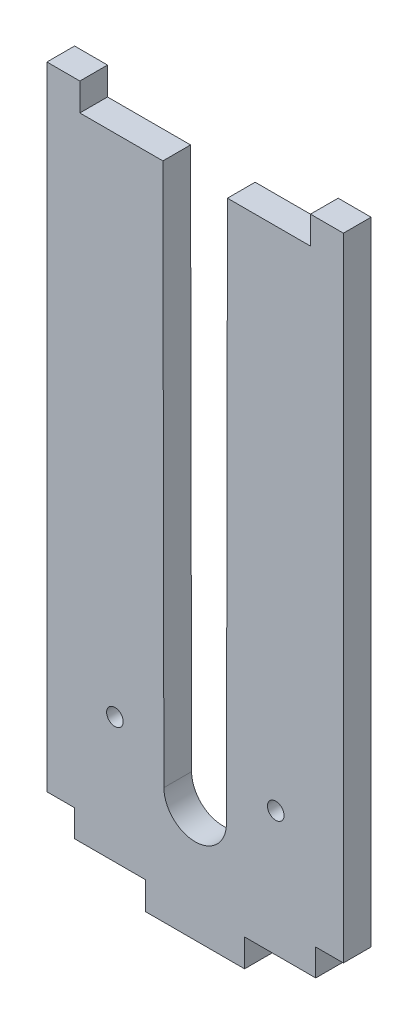
SolidWorks part; units mm, degrees
ref_plane "Front Plane" through (0, 0, 0) normal (0, 0, 1) x (1, 0, 0)
ref_plane "Top Plane" through (0, 0, 0) normal (0, 1, 0) x (1, 0, 0)
ref_plane "Right Plane" through (0, 0, 0) normal (1, 0, 0) x (0, 0, -1)
sketch "Sketch1" plane through (0, 0, 0) normal (0, 0, 1) x (1, 0, 0)
  line L1 (0, 0) -> (57.15, 0)
  line L2 (0, 0) -> (0, 127)
  line L3 (0, 127) -> (57.15, 127)
  line L4 (57.15, 0) -> (57.15, 127)
  dimension "D1" = 57.15
  dimension "D2" = 127
extrude "Boss-Extrude3" add sketch "Sketch1" along normal blind 5.334
sketch "Sketch3" plane through (0, 0, 5.334) normal (0, 0, 1) x (1, 0, 0)
  line L0 (22.352, 127) -> (0, 127)
  line L1 (57.15, 127) -> (0, 127) construction
  line L2 (57.15, 127) -> (34.798, 127)
  line L3 (28.575, 0) -> (28.575, 16.51) construction
  line L4 (0, 0) -> (57.15, 0) construction
  line L5 (34.798, 127) -> (34.6018, 22.479)
  line L6 (22.352, 127) -> (22.5482, 22.479)
  line L7 (28.575, 22.479) -> (28.575, 16.51)
  circle A0 centre (28.575, 22.479) radius 6.0268
  line M9 (57.15, 127) -> (0, 127)
  dimension "D1" = 22.352
  dimension "D2" = 22.352
  dimension "D3" = 16.51
  dimension "D4" = 5.969
extrude "Cut-Extrude2" cut sketch "Sketch3" against normal through all contours A0 L5 L6 M9 | A0 region at (28.575, 77.3496, 5.334) region at (28.575, 16.4692, 5.334)
sketch "Sketch8" plane through (0, 0, 0) normal (0, -1, 0) x (1, 0, 0)
  line L0 (0, 5.334) -> (57.15, 5.334) construction
  line L1 (57.15, 0) -> (38.1, 0)
  line L2 (57.15, 0) -> (57.15, 5.334)
  line L3 (57.15, 5.334) -> (38.1, 5.334)
  line L4 (38.1, 0) -> (38.1, 5.334)
  line L5 (0, 0) -> (57.15, 0) construction
  line L6 (19.05, 0) -> (0, 0)
  line L7 (19.05, 0) -> (19.05, 5.334)
  line L8 (19.05, 5.334) -> (0, 5.334)
  line L9 (0, 0) -> (0, 5.334)
  line L10 (38.1, 5.334) -> (19.05, 5.334) construction
extrude "Cut-Extrude6" cut sketch "Sketch8" against normal blind 5.334 contours L4 L3 L2 L1
extrude "Cut-Extrude7" cut sketch "Sketch8<5>" against normal blind 5.334
sketch "Sketch8<5>" plane through (0, 0, 0) normal (0, -1, 0) x (1, 0, 0) same geometry as "Sketch8"
sketch "Sketch16" plane through (0, 127, 0) normal (0, 1, 0) x (1, 0, 0)
  line L1 (34.798, 0) -> (57.15, 0)
  line L2 (34.798, 0) -> (34.798, -5.334)
  line L3 (34.798, -5.334) -> (57.15, -5.334)
  line L4 (57.15, 0) -> (57.15, -5.334)
  line L5 (0, 0) -> (22.352, 0)
  line L6 (0, 0) -> (0, -5.334)
  line L7 (0, -5.334) -> (22.352, -5.334)
  line L8 (22.352, 0) -> (22.352, -5.334)
extrude "Boss-Extrude4" add sketch "Sketch16" along normal blind 5.334
sketch "Sketch29" plane through (57.15, 0, 0) normal (1, 0, 0) x (0, 0, -1)
  line L0 (-5.334, 5.334) -> (-5.334, 132.334) construction
  line L1 (0, 5.334) -> (-5.334, 5.334)
  line L2 (0, 5.334) -> (0, 10.1282)
  line L3 (0, 10.1282) -> (-5.334, 10.1282)
  line L4 (-5.334, 5.334) -> (-5.334, 10.1282)
  line L5 (0, 10.1282) -> (0, 14.9225) construction
  line L6 (0, 5.334) -> (0, 132.334) construction
  line L7 (-4.7625, 14.9225) -> (-22.5425, 14.9225) construction
extrude "Cut-Extrude11" cut sketch "Sketch29" against normal blind 5.334
sketch "Sketch31" plane through (0, 0, 0) normal (-1, 0, 0) x (0, 0, 1)
  line L0 (5.334, 132.334) -> (5.334, 5.334) construction
  line L1 (0, 5.334) -> (5.334, 5.334)
  line L2 (0, 5.334) -> (0, 10.1282)
  line L3 (0, 10.1282) -> (5.334, 10.1282)
  line L4 (5.334, 5.334) -> (5.334, 10.1282)
  line L5 (0, 10.1282) -> (0, 14.9225) construction
  line L6 (0, 132.334) -> (0, 5.334) construction
  line L7 (4.7625, 14.9225) -> (22.5425, 14.9225) construction
extrude "Cut-Extrude12" cut sketch "Sketch31" against normal blind 5.334 contours L3 L4 L1 L2
sketch "Sketch32" plane through (0, 132.334, 0) normal (0, 1, 0) x (1, 0, 0)
  line L0 (0, -5.334) -> (22.352, -5.334) construction
  line L1 (0, 0) -> (6.35, 0)
  line L2 (0, 0) -> (0, -5.334)
  line L3 (0, -5.334) -> (6.35, -5.334)
  line L4 (6.35, 0) -> (6.35, -5.334)
  line L5 (34.798, -5.334) -> (57.15, -5.334) construction
  line L6 (57.15, 0) -> (50.8, 0)
  line L7 (57.15, 0) -> (57.15, -5.334)
  line L8 (57.15, -5.334) -> (50.8, -5.334)
  line L9 (50.8, 0) -> (50.8, -5.334)
  line L11 (6.35, 0) -> (22.352, 0)
  line L12 (6.35, 0) -> (6.35, -5.334)
  line L13 (6.35, -5.334) -> (22.352, -5.334)
  line L14 (22.352, 0) -> (22.352, -5.334)
  line L15 (34.798, -5.334) -> (50.8, -5.334)
  line L16 (34.798, -5.334) -> (34.798, 0)
  line L17 (34.798, 0) -> (50.8, 0)
  line L18 (50.8, -5.334) -> (50.8, 0)
  line M4 (0, -5.334) -> (22.352, -5.334)
  line M5 (22.352, -5.334) -> (22.352, 0)
  line M6 (22.352, 0) -> (0, 0)
  dimension "D1" = 6.35
  dimension "D2" = 6.35
extrude "Cut-Extrude13" cut sketch "Sketch32" against normal blind 5.334 contours L4 M6 M4 M5 | L17 L16 L15 L9 region at (14.351, 132.334, 2.667) region at (42.799, 132.334, 2.667)
sketch "Sketch33" plane through (0, 0, 0) normal (0, 0, -1) x (-1, 0, 0)
  line L0 (0, 132.334) -> (0, 10.1282) construction
  line L1 (-57.15, 10.1283) -> (-51.816, 10.1283)
  line L2 (-57.15, 10.1283) -> (-57.15, 10.5093)
  line L3 (-57.15, 10.5093) -> (-51.816, 10.5093)
  line L4 (-51.816, 10.1283) -> (-51.816, 10.5093)
  line L5 (-5.334, 10.1282) -> (0, 10.1282)
  line L6 (-5.334, 10.1282) -> (-5.334, 10.5092)
  line L7 (-5.334, 10.5092) -> (0, 10.5092)
  line L8 (0, 10.1282) -> (0, 10.5092)
  dimension "D1" = 0.381
  dimension "D2" = 0.381
extrude "Cut-Extrude14" cut sketch "Sketch33" against normal through all
sketch "Sketch35" plane through (0, 0, 5.334) normal (0, 0, 1) x (1, 0, 0)
  circle A0 centre (13.1076, 29.5507) radius 1.6
  circle A1 centre (44.1073, 29.4071) radius 1.6
extrude "Cut-Extrude15" cut sketch "Sketch35" against normal through all
equation "\"Foamcore\"= .1875in"
equation "\"Mdf\" = .21in"
equation "\"Gmaterial\"= \"Mdf\""
equation "\"D1@Boss-Extrude3\"= \"Gmaterial\""
equation "\"D1@Cut-Extrude6\"= \"Gmaterial\""
equation "\"D1@Cut-Extrude11\"=\"Gmaterial\""
equation "\"D1@Cut-Extrude7\"=\"Gmaterial\""
equation "\"D1@Cut-Extrude12\"= \"Gmaterial\""
equation "\"D1@Boss-Extrude4\"= \"Gmaterial\""
equation "\"D3@Sketch3\"= .65in"
equation "\"D1@Cut-Extrude13\"=\"Gmaterial\""
equation "\"D1@Sketch33\"=.015in"
equation "\"D2@Sketch33\"=.015in"
